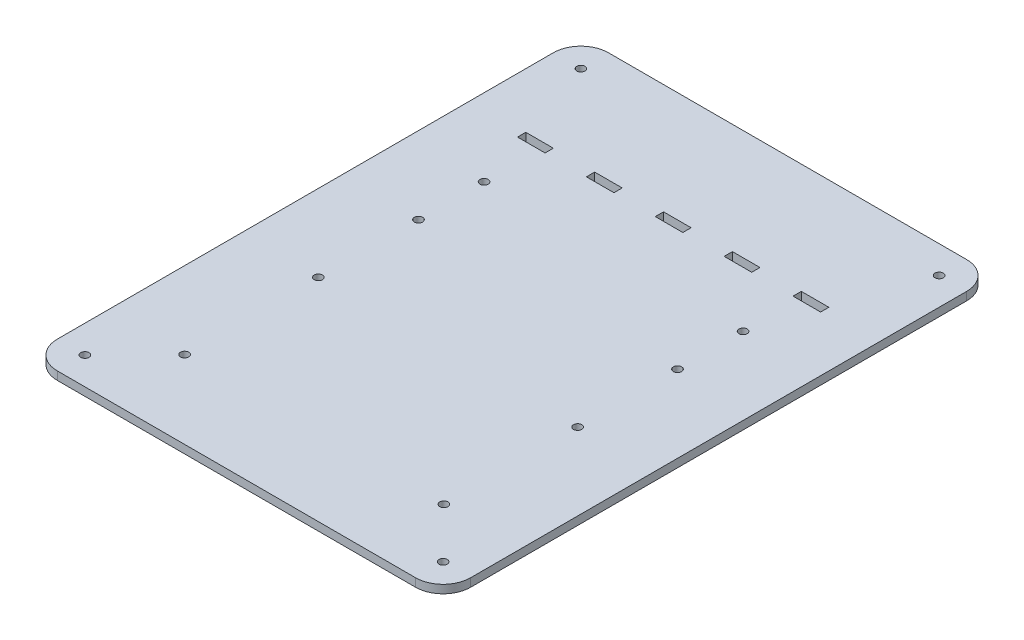
SolidWorks part; units mm, degrees
ref_plane "Спереди" through (0, 0, 0) normal (0, 0, 1) x (1, 0, 0)
ref_plane "Сверху" through (0, 0, 0) normal (0, 1, 0) x (1, 0, 0)
ref_plane "Справа" through (0, 0, 0) normal (1, 0, 0) x (0, 0, -1)
sketch "Эскиз1" plane through (0, 0, 0) normal (0, 1, 0) x (1, 0, 0)
  line L1 (75, -100) -> (-75, -100)
  line L2 (75, -100) -> (75, 100)
  line L3 (75, 100) -> (-75, 100)
  line L4 (-75, -100) -> (-75, 100)
  line L5 (75, -100) -> (-75, 100) construction
  line L6 (75, 100) -> (-75, -100) construction
  point P0 (0, 0)
  dimension "D1" = 200
  dimension "D2" = 150
extrude "Бобышка-Вытянуть1" add sketch "Эскиз1" along normal mid plane 3
fillet "Скругление1" radius 10 4 edges at (-75, 0, -100) (75, 0, -100) (75, 0, 100) (-75, 0, 100)
sketch "Эскиз2" plane through (0, 1.5, 0) normal (0, 1, 0) x (1, 0, 0)
  line L0 (0, 0) -> (0, -33.246) construction
  line L1 (0, 0) -> (-47.6996, 0) construction
  circle A0 centre (-65, 90) radius 1.5
  circle A1 centre (-65, -90) radius 1.5
  circle A2 centre (65, -90) radius 1.5
  circle A3 centre (65, 90) radius 1.5
extrude "Вырез-Вытянуть1" cut sketch "Эскиз2" against normal up to surface (3 mm away) up to face at (0, -1.5, 0)
sketch "Эскиз3" plane through (0, 1.5, 0) normal (0, 1, 0) x (1, 0, 0)
  line L0 (-45, 60) -> (-45, 57)
  line L4 (-55, 57) -> (-55, 60)
  line L5 (-20, 60) -> (-20, 57)
  line L6 (-30, 57) -> (-30, 60)
  line L14 (-45, 60) -> (-55, 60)
  line L15 (-20, 60) -> (-30, 60)
  line L16 (-20, 57) -> (-30, 57)
  line L17 (-45, 57) -> (-55, 57)
  line L19 (5, 60) -> (5, 57)
  line L20 (-5, 57) -> (-5, 60)
  line L23 (5, 60) -> (-5, 60)
  line L24 (5, 57) -> (-5, 57)
  line L27 (30, 60) -> (30, 57)
  line L28 (20, 57) -> (20, 60)
  line L30 (30, 60) -> (20, 60)
  line L31 (30, 57) -> (20, 57)
  line L32 (55, 60) -> (55, 57)
  line L33 (45, 57) -> (45, 60)
  line L34 (55, 60) -> (45, 60)
  line L35 (55, 57) -> (45, 57)
  line L36 (-75, 90) -> (-75, -90) construction
  line L38 (65, 100) -> (-65, 100) construction
  dimension "D1" = 3
  dimension "D2" = 5
  dimension "D3" = 10
  dimension "D4" = 20
  dimension "D5" = 40
extrude "Вырез-Вытянуть2" cut sketch "Эскиз3" against normal up to surface (3 mm away) contours L35 L32 L34 L33 | L31 L27 L30 L28 | L24 L19 L23 L20 | L16 L5 L15 L6 | L17 L0 L14 L4 region at (-50, 1.5, -58.5) region at (-25, 1.5, -58.5) region at (0, 1.5, -58.5) region at (25, 1.5, -58.5) region at (50, 1.5, -58.5) up to face at (65, -1.5, -88.5)
sketch "Sketch1" plane through (0, 1.5, 0) normal (0, 1, 0) x (1, 0, 0)
  circle A0 centre (-47.05, -23.23) radius 1.5
  circle A1 centre (-47.05, -71.77) radius 1.5
  circle A2 centre (47.05, -71.77) radius 1.5
  circle A3 centre (47.05, -23.23) radius 1.5
  circle A4 centre (-47, 36.8614) radius 1.5
  circle A5 centre (47, 36.8614) radius 1.5
  circle A6 centre (47, 13.0614) radius 1.5
  circle A7 centre (-47, 13.0614) radius 1.5
extrude "Cut-Extrude1" cut sketch "Sketch1" against normal up to next
